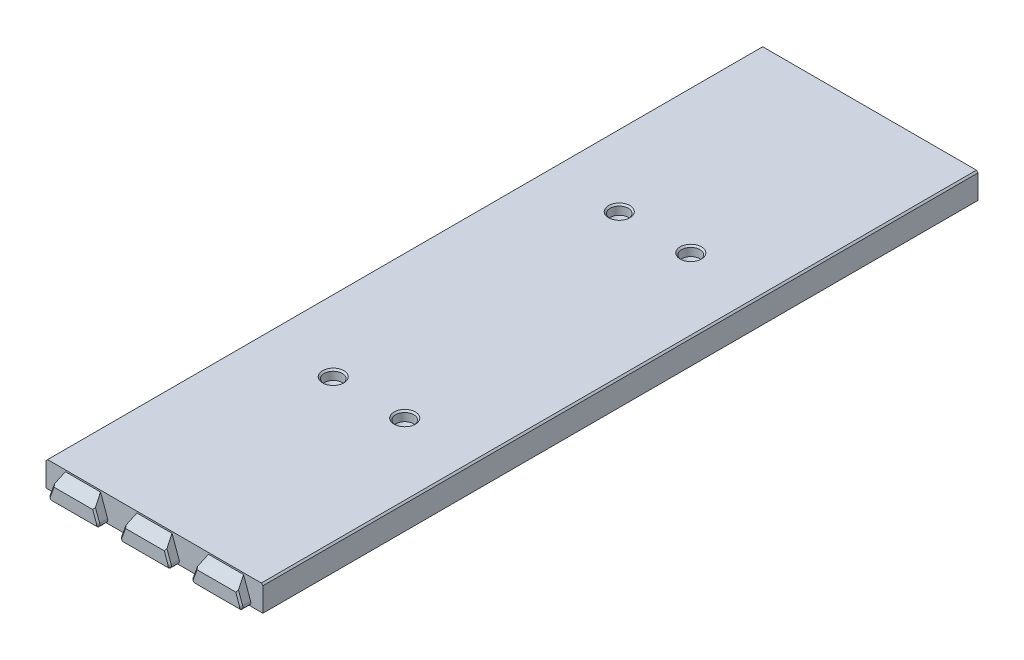
SolidWorks part; units mm, degrees
ref_plane "Front Plane" through (0, 0, 0) normal (0, 0, 1) x (1, 0, 0)
ref_plane "Top Plane" through (0, 0, 0) normal (0, 1, 0) x (1, 0, 0)
ref_plane "Right Plane" through (0, 0, 0) normal (1, 0, 0) x (0, 0, -1)
sketch "Sketch1" plane through (0, 0, 0) normal (0, 0, 1) x (1, 0, 0)
  line L0 (0, 0) -> (0, 8) construction
  line L1 (-34.125, 0) -> (0, 0) construction
  line L2 (-34.125, 0) -> (-34.125, 8)
  line L3 (-34.125, 8) -> (34.125, 8)
  line L5 (-34.125, 0) -> (-32.125, 0)
  line L6 (-32.125, 0) -> (-32.125, 6)
  line L7 (-32.125, 6) -> (32.125, 6)
  line L9 (32.125, 0) -> (32.125, 6)
  line L10 (34.125, 0) -> (32.125, 0)
  line L11 (34.125, 0) -> (34.125, 8)
  point P8 (0, 6)
  dimension "D2" = 6
  dimension "D1" = 34.125
  dimension "D3" = 2
  dimension "D4" = 2
extrude "Boss-Extrude1" add sketch "Sketch1" against normal blind 112.5
sketch "Sketch7" plane through (0, 0, 0) normal (0, 0, 1) x (1, 0, 0)
  line L2 (-32.125, 0) -> (32.125, 0)
  line L13 (-32.125, 0) -> (-32.125, 6)
  line L15 (-32.125, 6) -> (32.125, 6)
  line L16 (32.125, 0) -> (32.125, 6)
  line M3 (-32.125, 0) -> (-32.125, 6)
  line M4 (-32.125, 6) -> (32.125, 6)
  line M5 (32.125, 6) -> (32.125, 0)
extrude "Boss-Extrude7" add sketch "Sketch7" against normal blind 1 contours M4 M3 | M5 region at (0, 3, 0)
sketch "Sketch2" plane through (0, 0, 0) normal (0, 0, 1) x (1, 0, 0)
  line L14 (17.1618, 8) -> (14.25, 0)
  line L15 (34.125, 8) -> (-34.125, 8) construction
  line L16 (-34.125, 0) -> (34.125, 0) construction
  line L17 (14.25, 0) -> (30.75, 0)
  line L18 (17.1618, 8) -> (27.8382, 8)
  line L19 (-34.125, 0) -> (34.125, 0) construction
  line L21 (27.8382, 8) -> (30.75, 0)
  line L24 (11.25, 0) -> (11.25, 8) construction
  line L27 (-5.3382, 8) -> (-8.25, 0)
  line L28 (-5.3382, 8) -> (5.3382, 8)
  line L29 (-8.25, 0) -> (8.25, 0)
  line L30 (5.3382, 8) -> (8.25, 0)
  line L31 (-27.8382, 8) -> (-30.75, 0)
  line L32 (-27.8382, 8) -> (-17.1618, 8)
  line L33 (-30.75, 0) -> (-14.25, 0)
  line L34 (-17.1618, 8) -> (-14.25, 0)
  line L39 (17.1618, 8) -> (-5.3382, 8) construction
  line L40 (33.75, 8) -> (33.75, 0) construction
  line L41 (34.125, 0) -> (34.125, 8) construction
  line L42 (-33.75, 8) -> (-33.75, 0) construction
  line L43 (-34.125, 8) -> (-34.125, 0) construction
  point P22 (22.5, 8)
  point P23 (0, 8)
  dimension "D1" = 70
  dimension "D2" = 0.375
  dimension "D3" = 3
  dimension "D4" = 3
  dimension "D5" = 70
  dimension "D7" = 22.5
  dimension "D8" = 22.5
  dimension "D9" = 0.375
  dimension "D11" = 8
  dimension "D6" = 3
extrude "Boss-Extrude4" add sketch "Sketch2" along normal blind 3
sketch "Sketch8" plane through (0, 0, 0) normal (0, -1, 0) x (1, 0, 0)
  line L0 (-34.125, -22.5) -> (34.125, -22.5) construction
  line L1 (-32.6, -24.7417) -> (-32.6, -20.2583)
  line L2 (34.125, -112.5) -> (34.125, 0) construction
  line L3 (-34.125, 0) -> (-30.75, 0) construction
  line L4 (-32.75, -24.9559) -> (-32.75, -20.0441) construction
  line L5 (-32.75, -20.0441) -> (-28.75, -21.5) construction
  line L6 (-28.75, -21.5) -> (-28.75, -23.5) construction
  line L7 (-32.75, -112.5) -> (-32.75, -110.0441) construction
  line L8 (-32.75, -110.0441) -> (-28.75, -111.5) construction
  line L9 (-28.75, -111.5) -> (-28.75, -112.5) construction
  line L10 (-32.125, -112.5) -> (32.125, -112.5) construction
  line L11 (-28.75, -112.5) -> (-32.75, -112.5) construction
  line L12 (-32.75, -24.9559) -> (-28.75, -23.5) construction
  line L13 (0, -112.5) -> (0, 0) construction
  line L22 (-32.6, -20.2583) -> (-28.9, -21.605)
  line L23 (-34.125, -112.5) -> (-34.125, 0) construction
  line L28 (-34.125, -112.5) -> (-32.125, -112.5) construction
  line L33 (-28.9, -21.605) -> (-28.9, -23.395)
  line L34 (-32.6, -24.7417) -> (-28.9, -23.395)
  line L35 (-32.6, -112.35) -> (-32.6, -110.2583)
  line L36 (-32.6, -110.2583) -> (-28.9, -111.605)
  line L38 (-28.9, -112.35) -> (-32.6, -112.35) construction
  line L39 (-32.6, -112.35) -> (-32.6, -112.5)
  line L40 (-32.6, -112.5) -> (-28.9, -112.5)
  line L41 (-28.9, -112.5) -> (-28.9, -112.35)
  line L42 (-28.9, -112.35) -> (-28.9, -111.605)
  line L43 (32.6, -112.35) -> (32.6, -110.2583)
  line L44 (32.6, -112.35) -> (32.6, -112.5)
  line L45 (28.9, -112.5) -> (28.9, -112.35)
  line L46 (32.6, -24.7417) -> (28.9, -23.395)
  line L47 (28.9, -21.605) -> (28.9, -23.395)
  line L48 (32.6, -20.2583) -> (28.9, -21.605)
  line L49 (32.6, -24.7417) -> (32.6, -20.2583)
  line L50 (-28.9, -111.605) -> (-28.9, -112.35) construction
  line L51 (32.6, -112.5) -> (28.9, -112.5)
  line L52 (28.9, -112.35) -> (28.9, -111.605)
  line L53 (32.6, -110.2583) -> (28.9, -111.605)
  point P19 (-28.75, -22.5)
  dimension "D1" = 22.5
  dimension "D2" = 1.375
  dimension "D3" = 70
  dimension "D4" = 4
  dimension "D5" = 0.15
  dimension "D6" = 4
  dimension "D7" = 70
  dimension "D8" = 1
  dimension "D9" = 1
  dimension "D10" = 0.15
extrude "Boss-Extrude8" add sketch "Sketch8" against normal up to next and the other way blind 2
chamfer "Chamfer4" distance 0.5 angle 45 14 edges at (-28.9, -2, -112.0525) (28.9, -2, -112.0525) (30.75, -2, -110.9317) (32.6, -2, -111.3792) (-32.6, -2, -111.3792) (-30.75, -2, -110.9317) (28.9, -2, -22.5) (30.75, -2, -20.9317) (30.75, -2, -24.0683) (32.6, -2, -22.5) (-28.9, -2, -22.5) (-30.75, -2, -20.9317) (-32.6, -2, -22.5) (-30.75, -2, -24.0683)
fillet "Fillet4" radius 1 6 edges at (30.75, 0, 1.5) (14.25, 0, 1.5) (8.25, 0, 1.5) (-8.25, 0, 1.5) (-14.25, 0, 1.5) (-30.75, 0, 1.5)
chamfer "Chamfer6" distance 0.5 angle 45 15 edges at (15.9501, 4.671, 3) (29.0499, 4.671, 3) (22.5, 0, 3) (-29.0499, 4.671, 3) (-22.5, 0, 3) (-15.9501, 4.671, 3) (-6.5499, 4.671, 3) (6.5499, 4.671, 3) (0, 0, 3) (-30.141, 0.4264, 3) (-14.859, 0.4264, 3) (-7.641, 0.4264, 3) (7.641, 0.4264, 3) (14.859, 0.4264, 3) (30.141, 0.4264, 3)
fillet "Fillet2" radius 2 17 edges at (0, 6, -1) (-32.125, 3, -1) (32.125, 6, -10.7156) (32.125, 3, -1) (-32.125, 6, -10.7156) (-28.9, 6, -112.0525) (-30.5125, 6, -21.0181) (-28.9, 6, -22.5) (-30.5125, 6, -23.9819) (30.5125, 6, -23.9819) (28.9, 6, -22.5) (30.5125, 6, -21.0181) (32.125, 6, -67.5) (28.9, 6, -112.0525) (30.5125, 6, -111.0181) (-30.5125, 6, -111.0181) (-32.125, 6, -67.5)
mirror "Mirror2" about plane through (0, 0, -112.5) normal (0, 0, 1) of "Fillet4", "Boss-Extrude1", "Boss-Extrude7", "Boss-Extrude4", "Boss-Extrude8", "Chamfer4", "Fillet2", "Chamfer6"
sketch "Sketch9" plane through (0, 0, 0) normal (0, 1, 0) x (1, 0, 0)
  line L16 (0, 112.5) -> (0, 0) construction
  line L17 (-34.125, 112.5) -> (34.125, 112.5) construction
  line L20 (34.125, 225) -> (34.125, 0) construction
  line L21 (-34.125, 225) -> (-34.125, 0) construction
  circle A0 centre (-11.25, 67.5) radius 5
  circle A4 centre (11.25, 67.5) radius 5
  circle A5 centre (11.25, 157.5) radius 5
  circle A6 centre (-11.25, 157.5) radius 5
  point P23 (0, 112.5)
  point P24 (0, 112.5)
  dimension "D3" = 10
  dimension "D1" = 45
  dimension "D2" = 11.25
extrude "Boss-Extrude9" add sketch "Sketch9" along normal up to next
fillet "Fillet3" radius 3 4 edges at (-11.25, 6, -72.5) (-11.25, 6, -162.5) (11.25, 6, -162.5) (11.25, 6, -72.5)
sketch "Sketch10" plane through (0, 0, 0) normal (0, 1, 0) x (1, 0, 0)
  circle A0 centre (-11.25, 157.5) radius 1.85
  circle A1 centre (-11.25, 67.5) radius 1.85
  circle A2 centre (11.25, 67.5) radius 1.85
  circle A3 centre (11.25, 157.5) radius 1.85
  dimension "D1" = 3.7
extrude "Cut-Extrude2" cut sketch "Sketch10" along normal through all
sketch "Sketch11" plane through (0, 8, 0) normal (0, 1, 0) x (1, 0, 0)
  circle A0 centre (-11.25, 157.5) radius 2.85
  circle A1 centre (11.25, 157.5) radius 2.85
  circle A2 centre (11.25, 67.5) radius 2.85
  circle A3 centre (-11.25, 67.5) radius 2.85
  dimension "D1" = 5.7
extrude "Cut-Extrude3" cut sketch "Sketch11" against normal blind 3
chamfer "Chamfer7" distance 1 angle 45 4 edges at (11.25, 5, -155.65) (-11.25, 5, -155.65) (11.25, 5, -65.65) (-11.25, 5, -65.65)
sketch "Sketch12" plane through (0, 0, 0) normal (1, 0, 0) x (0, 0, -1)
  line L0 (0, 7.5) -> (-3, 4.5)
  line L1 (-3, 1.171) -> (-3, 8) construction
  line L2 (-3, 4.5) -> (-3, 7.5)
  line L4 (112.5, 8) -> (112.5, 0) construction
  line L5 (225, 8) -> (0, 8) construction
  line L6 (225, 0) -> (0, 0) construction
  line L10 (-3, 7.5) -> (0, 7.5) construction
  line L11 (0, 7.5) -> (0, 8)
  line L12 (0, 8) -> (-3, 8)
  line L13 (-3, 8) -> (-3, 7.5)
  line L14 (0, 0) -> (0, 8) construction
  line L15 (228, 7.5) -> (225, 7.5) construction
  line L16 (228, 8) -> (228, 7.5)
  line L17 (225, 8) -> (228, 8)
  line L18 (225, 7.5) -> (225, 8)
  line L19 (228, 4.5) -> (228, 7.5)
  line L20 (225, 7.5) -> (228, 4.5)
  dimension "D1" = 0.5
  dimension "D2" = 3
  dimension "D3" = 45
extrude "Cut-Extrude4" cut sketch "Sketch12" against normal through all both and the other way through all
chamfer "Chamfer8" distance 0.5 angle 45 6 edges at (-34.125, 8, -112.5) (34.125, 8, -112.5) (11.25, 8, -154.65) (-11.25, 8, -154.65) (11.25, 8, -64.65) (-11.25, 8, -64.65)
